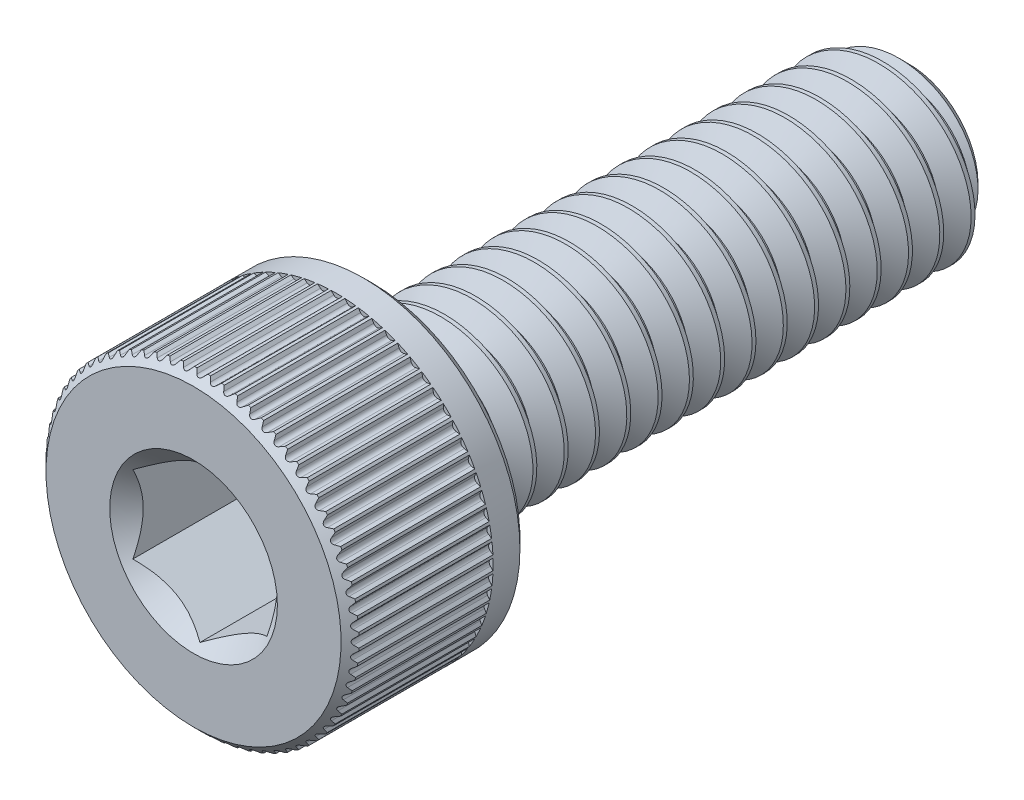
SolidWorks part; units mm, degrees
ref_plane "Front Plane" through (0, 0, 0) normal (0, 0, 1) x (1, 0, 0)
ref_plane "Top Plane" through (0, 0, 0) normal (0, 1, 0) x (1, 0, 0)
ref_plane "Right Plane" through (0, 0, 0) normal (1, 0, 0) x (0, 0, -1)
sketch "Sketch1" plane through (0, 0, 0) normal (1, 0, 0) x (0, 0, -1)
  line L0 (-8, 0) -> (8, 0) construction
  line L1 (8, 0) -> (8, 1.5453) construction
  line L2 (8, 1.5453) -> (7.5453, 2) construction
  line L3 (7.5453, 2) -> (7.475, 2) construction
  line L4 (7.475, 2) -> (-4, 2) construction
  line L5 (-4, 2) -> (-4, 3.5) construction
  line L6 (-4, 3.5) -> (-8, 3.5) construction
  line L7 (-8, 3.5) -> (-8, 0) construction
  line L8 (8, 1.5453) -> (8, 2) construction
  line L9 (7.9562, 2.0758) -> (8.3062, 1.4696) construction
  line L10 (8.3062, 1.4696) -> (8.6562, 2.0758) construction
  line L11 (8.6562, 2.0758) -> (7.9562, 2.0758) construction
  line L12 (8.3062, 2.0758) -> (8.3062, 2) construction
  line L13 (8.3062, 1.4696) -> (8.3062, 1.5453) construction
  line L14 (8.2625, 1.5453) -> (8.35, 1.5453) construction
  line L15 (8, 2) -> (8.6125, 2) construction
  line L16 (7.9781, 2.0379) -> (8.6344, 2.0379) construction
  line L17 (8, 0) -> (8, -2) construction
  line L18 (-4.2, 3.5) -> (-4, 3.3) construction
  line L19 (-7.8, 3.5) -> (-8, 3.3) construction
  line L20 (-4, 2) -> (-4, 0) construction
  line L21 (-4, 1) -> (0, 1) construction
  line L22 (0, 1) -> (4, 1) construction
  line L23 (4, 1) -> (8, 1) construction
  line L24 (0, 1) -> (0, 2) construction
  line L25 (0, 2) -> (0, 3.5) construction
  line L26 (4, 1) -> (4, 3.5) construction
  point P0 (-8, 1.5)
  point P3 (6.25, 2)
  point P4 (0, 0)
  point P18 (4, 2)
  point P22 (8.3062, 1.5453)
  point P24 (7.475, 2)
  point P25 (8.3062, 2)
  point P28 (8.3062, 2.0379)
  point P29 (6.25, -2)
  point P30 (0, 2)
  point P31 (-6, 3.5)
  point P37 (-4.7, 3.5)
  point P38 (-7.7, 3.5)
  point P45 (0, 1)
  point P46 (4, 1)
  dimension "D2" = 0.0875
  dimension "D7" = 0.2
  dimension "D8" = 0.2
  dimension "D9" = 0.2
  dimension "D10" = 0.1
  dimension "D11" = 0.5
  dimension "Drive Size" = 3
  dimension "Head Diameter" = 7
  dimension "Head Height" = 4
  dimension "Thread Pitch" = 0.7
  dimension "Thread Size" = 4
  dimension "Length" = 12
  dimension "D12" = 0.525
  dimension "D4" = 1.75
  dimension "D3" = 45
sketch "Sketch2" plane through (0, 0, 0) normal (1, 0, 0) x (0, 0, -1)
  line L0 (-8, 0) -> (-8, 3.3)
  line L1 (-7.8, 3.5) -> (-4.2, 3.5)
  line L2 (-4, 3.3) -> (-4, 2.2)
  line L4 (7.5453, 2) -> (8, 1.5453)
  line L5 (8, 1.5453) -> (8, 0)
  line L6 (-4, 3.5) -> (-8, 3.5) construction
  line L7 (8, 0) -> (-8, 0)
  line L8 (-7.8, 3.5) -> (-8, 3.3) construction
  line L10 (-7.8, 3.5) -> (-8, 3.3)
  line L14 (-4.2, 3.5) -> (-4, 3.3) construction
  line L16 (-4.2, 3.5) -> (-4, 3.3)
  line L17 (-4, 2) -> (-4, 3.5) construction
  line L19 (-3.8, 2) -> (7.5453, 2)
  line L20 (7.475, 2) -> (-4, 2) construction
  arc A1 (-4, 2.2) -> (-3.8, 2) centre (-3.8, 2.2) ccw
  dimension "D3" = 0.2
revolve "Revolve1" add sketch "Sketch2" angle 360 about L7
sketch "Sketch3" plane through (0, 0, 8) normal (0, 0, 1) x (1, 0, 0)
  line L1 (1.5, -0.866) -> (1.5, 0.866)
  line L2 (1.5, 0.866) -> (0, 1.7321)
  line L3 (0, 1.7321) -> (-1.5, 0.866)
  line L4 (-1.5, 0.866) -> (-1.5, -0.866)
  line L5 (-1.5, -0.866) -> (0, -1.7321)
  line L6 (0, -1.7321) -> (1.5, -0.866)
  circle A0 centre (0, 0) radius 1.5 construction
  circle A1 centre (0, 0) radius 3.5 construction
  circle A2 centre (0, 0) radius 3.5 construction
  circle A3 centre (0, 0) radius 1.7321 construction
  point P13 (0, 0)
extrude "Cut-Extrude1" cut sketch "Sketch3" against normal offset from surface (3 mm away) 1 up to face at (0, 3.3, 4)
sketch "Sketch4" plane through (0, 0, 8) normal (0, 0, 1) x (1, 0, 0)
  circle A0 centre (0, 0) radius 1.875
  dimension "D1" = 3.75
extrude "Cut-Extrude2" cut sketch "Sketch4" against normal up to vertex (2 mm away) draft 45 up to point (0, 3.5, 6)
sketch "Sketch11" plane through (0, 0, 0) normal (1, 0, 0) x (0, 0, -1)
  line L0 (-8, 0) -> (8, 0) construction
  line L1 (-8, 0) -> (8, 0) construction
  line L2 (-1.75, 0) -> (-1.75, 2) construction
  line L3 (7.475, 2) -> (-4, 2) construction
  line L4 (5.75, 0) -> (5.75, 2) construction
  line L6 (8, 1.5453) -> (8, 2) construction
  point P2 (-1.75, 0)
  point P3 (5.75, 0)
  dimension "D1" = 2.25
  dimension "D2" = 2.25
sketch "Sketch6" plane through (0, 0, -8) normal (0, 0, -1) x (-1, 0, 0)
  circle A0 centre (0, 0) radius 2
curve "Helix/Spiral1" pitch 0.7 height 12.7 turns 18.1429
sketch "Sketch10" plane through (0, 0, 0) normal (1, 0, 0) x (0, 0, -1)
  line L0 (-3.8, -3.5) -> (-3.8, 3.5)
  line L5 (-8, 0) -> (8, 0) construction
  line L6 (-3.8, 2) -> (-3.8, -2) construction
  point P3 (-3.8, 0)
split "Split1" trim tools "Sketch10" bodies to split 106 resulting bodies 114 115
sketch "Sketch7" plane through (0, 0, 0) normal (1, 0, 0) x (0, 0, -1)
  line L0 (7.9781, 2.0379) -> (8.6344, 2.0379)
  line L1 (8.6344, 2.0379) -> (8.35, 1.5453)
  line L2 (8.35, 1.5453) -> (8.2625, 1.5453)
  line L3 (8.2625, 1.5453) -> (7.9781, 2.0379)
sweep "Cut-Sweep1" cut profiles "Sketch7" path "Helix/Spiral1"
sketch "Sketch8" plane through (0, 0, 0) normal (1, 0, 0) x (0, 0, -1)
  line L0 (-4, 0) -> (-4, 2)
  line L1 (-3.8, -2) -> (-3.8, 2) construction
  line L2 (-4, 2) -> (-3.8, 2)
  line L4 (-3.8, 2) -> (-2.6453, 0)
  line L5 (-2.6453, 0) -> (-4, 0)
  line L6 (7.475, 2) -> (-4, 2) construction
  line L7 (-8, 0) -> (8, 0) construction
  dimension "D1" = 60
revolve "Revolve2" add sketch "Sketch8" angle 360 about L5
ref_plane "Plane1" through (0, 0, 8) normal (0, 0, 1) x (1, 0, 0)
sketch "Sketch12" plane through (0, 0, 8) normal (0, 0, 1) x (1, 0, 0)
  line L0 (0, 0) -> (0.1221, 3.4979) construction
  line L1 (0, 0) -> (-0.1221, 3.4979) construction
  line L2 (0, 3.4125) -> (0, 3.5875) construction
  line L3 (-0.2118, 3.5875) -> (0.2118, 3.5875)
  line L4 (-0.2118, 3.5875) -> (-0.0628, 3.4385)
  line L5 (0.0628, 3.4385) -> (0.2118, 3.5875)
  circle A0 centre (0, 0) radius 3.5 construction
  arc A1 (-0.0628, 3.4385) -> (0.0628, 3.4385) centre (0, 3.5013) ccw
  point P9 (0, 3.5875)
  point P13 (0, 3.5)
  dimension "D1" = 4
  dimension "D2" = 0.0875
extrude "Cut-Extrude3" cut sketch "Sketch12" against normal blind 3.2
pattern_circular "CirPattern1" count 72 over 360 about axis through (0, 0, 0) along (0, 0, 1) of "Cut-Extrude3"
equation "\"D2@Sketch1\" = \"Thread Pitch@Sketch1\" / 8"
equation "\"D4@Helix/Spiral1\" = \"Thread Pitch@Sketch1\""
equation "\"D7@Sketch1\" = \"Head Height@Sketch1\" * .05"
equation "\"D8@Sketch1\"=\"D7@Sketch1\""
equation "\"D9@Sketch1\"=\"D7@Sketch1\""
equation "\"D10@Sketch1\"=\"D7@Sketch1\"/2"
equation "\"D11@Sketch1\"=\"D10@Sketch1\"*5"
equation "\"D4@Sketch1\"=\"Thread Pitch@Sketch1\"*2.5"
equation "\"D12@Sketch1\"=\"Thread Pitch@Sketch1\"*.75"
equation "\"D3@Helix/Spiral1\"=\"Length@Sketch1\"+\"Thread Pitch@Sketch1\""
equation "\"D3@Sketch2\" = \"Thread Size@Sketch1\" * 0.05"
equation "\"D1@Sketch11\"=\"Length@Sketch1\"*0.1875"
equation "\"D2@Sketch11\"=\"D1@Sketch11\""
equation "\"D2@Sketch12\"=\"Head Diameter@Sketch1\"*.0125"
equation "\"D1@Cut-Extrude3\"=\"Head Height@Sketch1\"*.8"
equation "\"D1@CirPattern1\"=\"D3@CirPattern1\"/(1.25*\"D1@Sketch12\")"
equation "\"D1@Sketch4\"=\"Drive Size@Sketch1\"*1.25"
